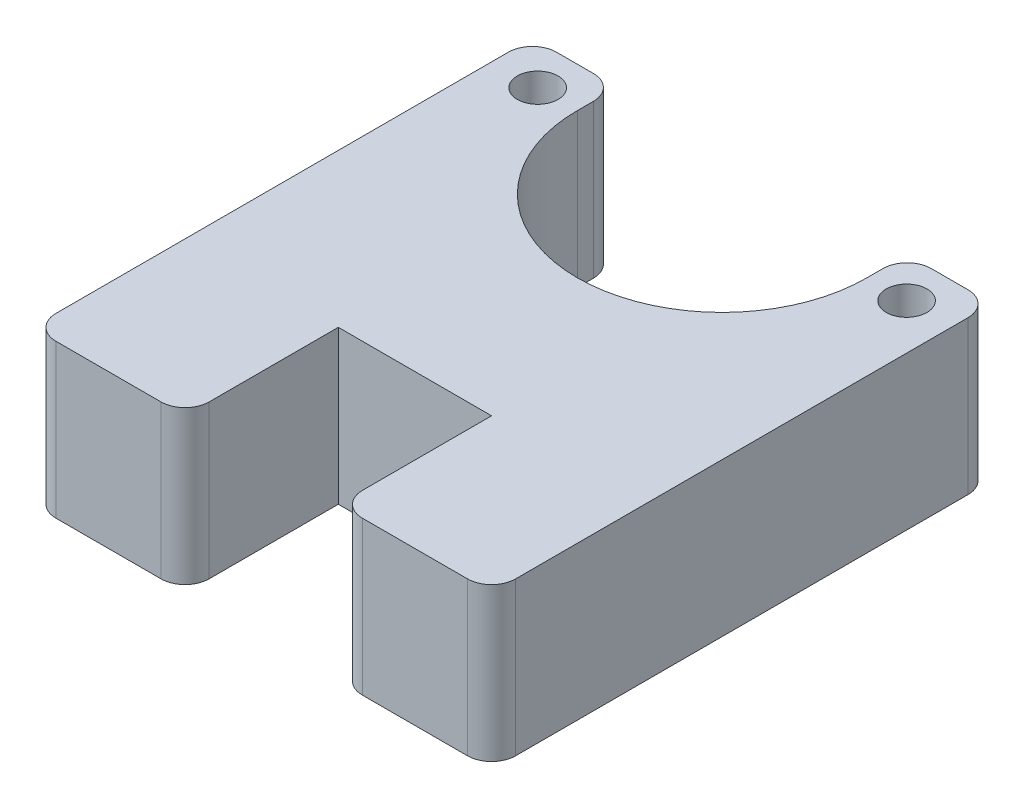
SolidWorks part; units mm, degrees
ref_plane "Front Plane" through (0, 0, 0) normal (0, 0, 1) x (1, 0, 0)
ref_plane "Top Plane" through (0, 0, 0) normal (0, 1, 0) x (1, 0, 0)
ref_plane "Right Plane" through (0, 0, 0) normal (1, 0, 0) x (0, 0, -1)
sketch "Sketch1" plane through (0, 0, 0) normal (0, 1, 0) x (1, 0, 0)
  line L0 (0, 0) -> (0, 6.0001)
  line L1 (0, 0) -> (19.05, 0)
  line L2 (0, 6.0001) -> (19.05, 6.0001)
  line L3 (19.05, 0) -> (19.05, 6.0001)
  line L4 (0, 6.0001) -> (0, 14.3937)
  line L5 (0, 6.0001) -> (3.525, 6.0001)
  line L6 (0, 14.3937) -> (3.525, 14.3937)
  line L7 (3.525, 6.0001) -> (3.525, 14.3937)
  line L8 (19.05, 6.0001) -> (19.05, 14.3937)
  line L9 (19.05, 6.0001) -> (15.525, 6.0001)
  line L10 (19.05, 14.3937) -> (15.525, 14.3937)
  line L11 (15.525, 6.0001) -> (15.525, 14.3937)
  line L12 (0, 0) -> (6.35, 0)
  line L13 (0, 0) -> (0, -6.35)
  line L14 (6.35, 0) -> (6.35, -6.35)
  line L15 (0, -6.35) -> (6.35, -6.35)
  line L16 (19.05, 0) -> (12.7, 0)
  line L17 (19.05, 0) -> (19.05, -6.35)
  line L18 (12.7, 0) -> (12.7, -6.35)
  line L19 (19.05, -6.35) -> (12.7, -6.35)
  arc A0 (3.525, 12.7287) -> (15.525, 12.7287) centre (9.525, 12.7287) ccw
  circle A1 centre (17.1675, 12.7287) radius 0.845
  circle A2 centre (1.8825, 12.7287) radius 0.845
  point P8 (9.525, 6.0001)
  dimension "D6" = 1.69
  dimension "D1" = 6.0001
  dimension "D2" = 6.35
  dimension "D3" = 6.7286
  dimension "D4" = 6
  dimension "D5" = 1.665
  dimension "D7" = 1.6425
  dimension "D9" = 6.35
  dimension "D10" = 6.35
  dimension "D11" = 6.35
  dimension "D12" = 6.35
  dimension "D13" = 1.6425
extrude "Boss-Extrude1" add sketch "Sketch1" along normal blind 6.35 contours L2 L7 L6 L4 A2 | A0 L7 L2 L11 | L11 L2 L8 L10 A1 | L1 L3 L2 L0 | L13 L15 L14 L1 | L19 L17 L1 L18 region at (9.525, 0, -3) region at (3.175, 0, 3.175) region at (1.7527, 0, -9.9892) region at (3.6626, 0, -9.3644) region at (15.875, 0, 3.175) region at (17.2973, 0, -9.9892)
fillet "Fillet3" radius 1 8 edges at (19.05, 3.175, 6.35) (12.7, 3.175, 6.35) (6.35, 3.175, 6.35) (0, 3.175, 6.35) (19.05, 3.175, -14.3937) (15.525, 3.175, -14.3937) (3.525, 3.175, -14.3937) (0, 3.175, -14.3937)
equation "\"vigorwidth\"= 0.472441in"
equation "\"vigorflangewidth\"= 0.731102in"
equation "\"vigorflangelength\"= 0.131102in"
equation "\"vigorscrewsize\"= 0.066535in"
equation "\"vigorholeoffsetwid\"= 0.0646653in"
equation "\"vigorholeoffsetlen\"= 0.065551in"
equation "\"vigorflangedepth\"= 0.0901575in"
equation "\"vigordiscdepth\"= 0.0492126in"
equation "\"vigormotordepth\"= 1.12362in"
equation "\"vigortipdepth\"= 0.259055in"
equation "\"vigoraxlewidth\"= 0.173622in"
equation "\"vigorcutlen\"= 0.0480315in"
equation "\"vigoraxledepth\"= 0.159055in"
equation "\"D4@Sketch1\"=\"vigorwidth\"/2"
equation "\"rackoffset\"=.236224in"
equation "\"D1@Sketch1\"=\"rackoffset\""
equation "\"Slot\"=.25in"
equation "\"D10@Sketch1\"=\"Slot\""
equation "\"D9@Sketch1\"=\"Slot\""
equation "\"MotorMountLegLength\"=.25in"
equation "\"D11@Sketch1\"=\"MotorMountLegLength\""
equation "\"D12@Sketch1\"=\"MotorMountLegLength\""
equation "\"GearOffset\"=.264907in"
equation "\"D3@Sketch1\"=\"GearOffset\""
equation "\"D7@Sketch1\"=\"vigorholeoffsetwid\""
equation "\"D13@Sketch1\"=\"vigorholeoffsetwid\""
equation "\"D5@Sketch1\"=\"vigorflangelength\"/2"
equation "\"SlotSpacing\"=.25in"
equation "\"D2@Sketch1\"=\"SlotSpacing\""
equation "\"D6@Sketch1\"=\"vigorscrewsize\""
